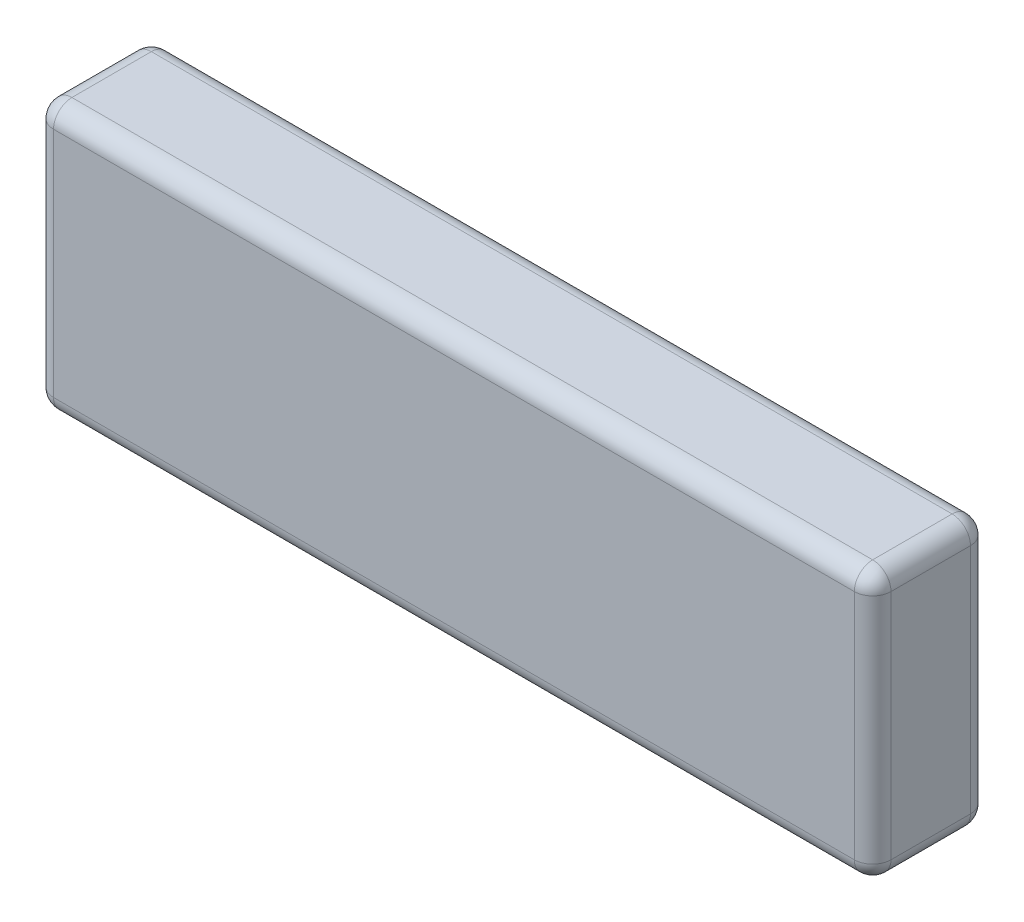
SolidWorks part; units mm, degrees
material "Acrílico (Impacto medio-alto)"
ref_plane "Alzado" through (0, 0, 0) normal (0, 0, 1) x (1, 0, 0)
ref_plane "Planta" through (0, 0, 0) normal (0, 1, 0) x (1, 0, 0)
ref_plane "Vista lateral" through (0, 0, 0) normal (1, 0, 0) x (0, 0, -1)
sketch "Croquis2" plane through (0, 0, 0) normal (0, 0, 1) x (1, 0, 0)
  line L1 (68.5, -22) -> (-68.5, -22)
  line L2 (68.5, -22) -> (68.5, 22)
  line L3 (68.5, 22) -> (-68.5, 22)
  line L4 (-68.5, -22) -> (-68.5, 22)
  line L5 (68.5, -22) -> (-68.5, 22) construction
  line L6 (68.5, 22) -> (-68.5, -22) construction
  point P0 (0, 0)
  dimension "D1" = 137
  dimension "D2" = 44
extrude "Saliente-Extruir1" add sketch "Croquis2" along normal blind 19
fillet "Redondeo3" radius 3 1 edges at (0, -22, 0) type face fillet first side face at (0, -22, 9.5) second side face at (0, 0, 0)
fillet "Redondeo4" radius 3 1 edges at (0, -22, 19) type face fillet first side face at (0, -22, 11) second side face at (0, 0, 19)
fillet "Redondeo5" radius 3 2 edges at (-68.5, 22, 9.5) (0, 22, 19) type face fillet first side face at (-68.5, -6.5404, 9.5) first side face at (0, 1.5, 19) second side face at (0, 22, 9.5)
fillet "Redondeo6" radius 3 2 edges at (-68.5, 0, 19) (-68.5, -22, 9.5) type face fillet first side face at (0, -22, 9.5) first side face at (0, 0, 19) second side face at (-68.5, -7.5404, 9.5)
fillet "Redondeo7" radius 3 3 edges at (68.5, -22, 9.5) (68.5, 0, 0) (68.5, 22, 9.5) type face fillet first side face at (1.5, 22, 9.5) first side face at (1.5, -22, 9.5) first side face at (1.5, 0, 0) second side face at (1.5, 0, 19) second side face at (68.5, 0, 9.5)
